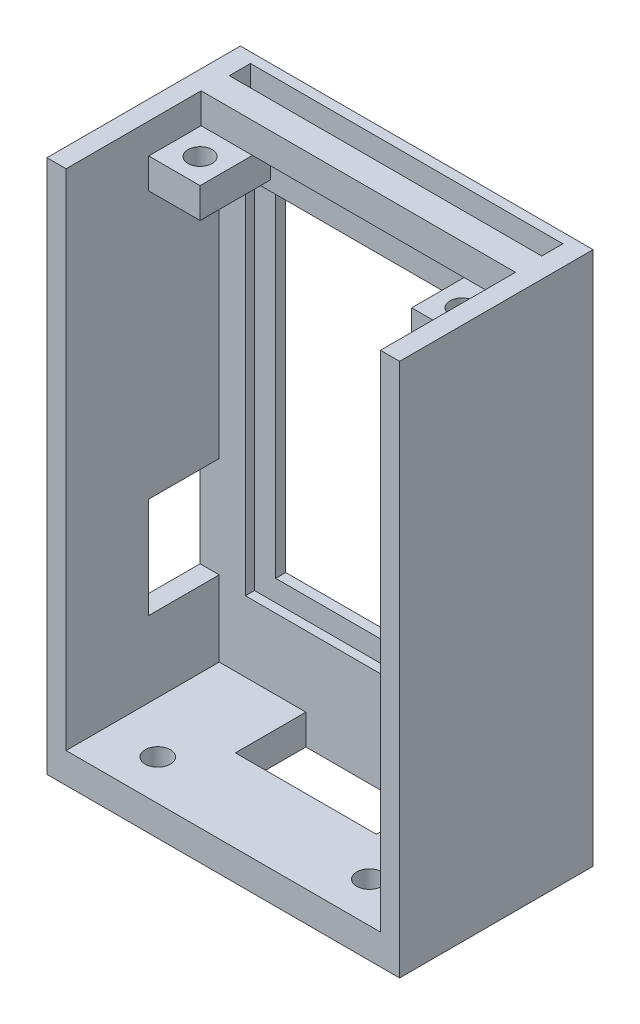
SolidWorks part; units mm, degrees
ref_plane "前视基准面" through (0, 0, 0) normal (0, 0, 1) x (1, 0, 0)
ref_plane "上视基准面" through (0, 0, 0) normal (0, 1, 0) x (1, 0, 0)
ref_plane "右视基准面" through (0, 0, 0) normal (1, 0, 0) x (0, 0, -1)
sketch "草图1" plane through (0, 0, 0) normal (0, 0, 1) x (1, 0, 0)
  line L1 (-15, 20) -> (20, 20)
  line L2 (-15, 20) -> (-15, -33)
  line L3 (-15, -33) -> (20, -33)
  line L4 (20, 20) -> (20, -33)
  dimension "D1" = 53
  dimension "D2" = 35
  dimension "D3" = 15
  dimension "D4" = 20
extrude "凸台-拉伸1" add sketch "草图1" along normal blind 2
sketch "草图2" plane through (0, 0, 2) normal (0, 0, 1) x (1, 0, 0)
  line L0 (-15, 20) -> (-15, -33)
  line L1 (-15, -33) -> (-13, -33)
  line L2 (-15, -33) -> (20, -33) construction
  line L3 (-13, -33) -> (-13, 20)
  line L4 (20, 20) -> (-15, 20) construction
  line L5 (-13, 20) -> (-15, 20)
  line L6 (20, 20) -> (20, -33)
  line L7 (20, -33) -> (18, -33)
  line L8 (18, -33) -> (18, 20)
  line L9 (18, 20) -> (20, 20)
  dimension "D1" = 2
  dimension "D2" = 2
extrude "凸台-拉伸2" add sketch "草图2" along normal blind 13.2
sketch "草图3" plane through (0, 0, 2) normal (0, 0, 1) x (1, 0, 0)
  line L0 (-13, 20) -> (-13, 17)
  line L1 (-13, -33) -> (-13, 20) construction
  line L2 (-13, 17) -> (18, 17)
  line L3 (18, 20) -> (18, -33) construction
  line L4 (18, 17) -> (18, 20)
  line L5 (18, 20) -> (-13, 20)
  line L6 (18, -33) -> (-13, -33)
  line L7 (-13, -33) -> (-13, -30)
  line L8 (-13, -30) -> (18, -30)
  line L9 (18, -30) -> (18, -33)
  dimension "D1" = 3
  dimension "D2" = 3
extrude "凸台-拉伸3" add sketch "草图3" along normal blind 7.2
sketch "草图4" plane through (0, 0, 2) normal (0, 0, 1) x (1, 0, 0)
  line L0 (-13, 17) -> (-13, 14)
  line L1 (-13, -30) -> (-13, 17) construction
  line L2 (-13, 14) -> (18, 14)
  line L3 (18, 17) -> (18, -30) construction
  line L4 (18, 14) -> (18, 17)
  line L5 (18, 17) -> (-13, 17)
  line L6 (-13, -30) -> (18, -30)
  line L7 (18, -30) -> (18, -27)
  line L8 (18, -27) -> (-13, -27)
  line L9 (-13, -27) -> (-13, -30)
  dimension "D1" = 3
  dimension "D2" = 3
extrude "凸台-拉伸4" add sketch "草图4" along normal up to surface (13.2 mm away) up to face at (-14, -6.5, 15.2)
sketch "草图5" plane through (0, 17, 0) normal (0, 1, 0) x (1, 0, 0)
  line L0 (-13, -9.2) -> (18, -9.2) construction
  line L1 (-13, -15.2) -> (-13, -9.2) construction
  line L2 (18, -15.2) -> (18, -9.2) construction
  circle A0 centre (-8, -11.2) radius 1.25
  circle A1 centre (2.5, -11.2) radius 1.25
  circle A2 centre (13, -11.2) radius 1.25
  dimension "D2" = 2.5
  dimension "D3" = 2.5
  dimension "D6" = 2.5
  dimension "D1" = 2
  dimension "D4" = 2
  dimension "D5" = 2
  dimension "D7" = 5
  dimension "D8" = 5
  dimension "D9" = 10.5
extrude "切除-拉伸1" cut sketch "草图5" against normal up to next
sketch "草图7" plane through (0, 0, 15.2) normal (0, 0, 1) x (1, 0, 0)
  line L0 (-13, 17) -> (-13, 14)
  line L1 (-13, 14) -> (18, 14)
  line L2 (18, 14) -> (18, 17)
  line L3 (18, 17) -> (-13, 17)
extrude "切除-拉伸2" cut sketch "草图7" against normal blind 2.2
sketch "草图8" plane through (0, 0, 15.2) normal (0, 0, 1) x (1, 0, 0)
  line L0 (-13, -27) -> (-13, -30)
  line L1 (-13, -30) -> (18, -30)
  line L2 (18, -30) -> (18, -27)
  line L3 (18, -27) -> (-13, -27)
extrude "切除-拉伸3" cut sketch "草图8" against normal blind 2
sketch "草图9" plane through (0, -30, 0) normal (0, -1, 0) x (1, 0, 0)
  line L0 (18, 9.2) -> (-13, 9.2) construction
  line L1 (-13, 13.2) -> (-13, 9.2) construction
  line L2 (18, 13.2) -> (18, 9.2) construction
  circle A0 centre (-8, 11.2) radius 1.25
  circle A1 centre (13, 11.2) radius 1.25
  line M1 (18, 13.2) -> (-13, 13.2)
  line M2 (-13, 13.2) -> (-13, 9.2)
  line M3 (-13, 9.2) -> (18, 9.2)
  line M4 (18, 9.2) -> (18, 13.2)
  dimension "D3" = 2.5
  dimension "D4" = 2.5
  dimension "D1" = 2
  dimension "D2" = 2
  dimension "D5" = 5
  dimension "D6" = 5
sketch "草图10" plane through (0, 0, 13.2) normal (0, 0, 1) x (1, 0, 0)
  line L0 (-3, -27) -> (-3, -30)
  line L1 (18, -27) -> (-13, -27) construction
  line L2 (-13, -30) -> (18, -30) construction
  line L3 (-3, -30) -> (8, -30)
  line L4 (18, -30) -> (-13, -30) construction
  line L5 (8, -30) -> (8, -27)
  line L6 (18, -27) -> (-13, -27) construction
  line L7 (8, -27) -> (-3, -27)
  line L8 (-13, -27) -> (-13, -30) construction
  line L9 (18, -30) -> (18, -27) construction
  dimension "D1" = 10
  dimension "D2" = 10
extrude "切除-拉伸4" cut sketch "草图10" against normal up to surface (4 mm away) up to face at (2.5, -31.5, 9.2)
extrude "切除-拉伸5" cut sketch "草图9" against normal up to surface (3 mm away) contours A0 | A1 region at (-8, -30, 11.2) region at (13, -30, 11.2) up to face at (2.5, -27, 9.4)
sketch "草图12" plane through (0, 0, 15.2) normal (0, 0, 1) x (1, 0, 0)
  line L0 (-15, -22.5) -> (-13, -22.5)
  line L1 (-15, 20) -> (-15, -33) construction
  line L2 (-13, -27) -> (-13, 14) construction
  line L3 (-13, -22.5) -> (-13, -12.5)
  line L4 (-13, -12.5) -> (-15, -12.5)
  line L5 (-15, -12.5) -> (-15, -22.5)
  line L6 (-15, -33) -> (-13, -33) construction
  dimension "D1" = 10.5
  dimension "D2" = 10
sketch "草图13" plane through (0, 0, 2) normal (0, 0, 1) x (1, 0, 0)
  line L0 (-13, -27) -> (-13, 14) construction
  line L1 (-14, 17) -> (19, 17)
  line L2 (-14, 17) -> (-14, -30)
  line L3 (-14, -30) -> (19, -30)
  line L4 (19, 17) -> (19, -30)
  line L5 (-13, 14) -> (18, 14) construction
  dimension "D1" = 33
  dimension "D2" = 47
  dimension "D3" = 1
  dimension "D4" = 3
sketch "草图14" plane through (0, 0, 9.2) normal (0, 0, 1) x (1, 0, 0)
  line L0 (-13, 20) -> (18, 20)
  line L1 (18, 20) -> (18, 17)
  line L2 (18, 17) -> (-13, 17)
  line L3 (-13, 17) -> (-13, 20)
extrude "切除-拉伸8" cut sketch "草图14" against normal blind 5
sketch "草图15" plane through (0, 0, 0) normal (0, 0, -1) x (-1, 0, 0)
  line L0 (15, -33) -> (-20, -33) construction
  line L1 (10.5, -23) -> (-15.5, -23)
  line L2 (10.5, -23) -> (10.5, 13)
  line L3 (10.5, 13) -> (-15.5, 13)
  line L4 (-15.5, -23) -> (-15.5, 13)
  line L5 (15, 20) -> (15, -33) construction
  line M3 (15, -33) -> (15, 20)
  line M4 (15, 20) -> (-20, 20)
  line M5 (-20, 20) -> (-20, -33)
  line M6 (-20, -33) -> (15, -33)
  dimension "D1" = 26
  dimension "D2" = 36
  dimension "D3" = 10
  dimension "D4" = 4.5
extrude "凸台-拉伸5" add sketch "草图15" along normal blind 1 contours L1 L4 L3 L2 M6 M3 M4 M5 region at (2.5, -32.3649, 0)
extrude "切除-拉伸9" cut sketch "草图15<3>" against normal up to surface (2 mm away) up to face at (2.5, -6.5, 2)
sketch "草图15<3>" plane through (0, 0, 0) normal (0, 0, -1) x (-1, 0, 0) same geometry as "草图15"
extrude "凸台-拉伸6" add sketch "草图15<4>" along normal blind 1 contours L1 L4 L3 L2 M6 M3 M4 M5 region at (2.5, -32.3649, 0)
sketch "草图15<4>" plane through (0, 0, 0) normal (0, 0, -1) x (-1, 0, 0) same geometry as "草图15"
extrude "切除-拉伸10" cut sketch "草图14<2>" against normal up to surface (7.2 mm away) up to face at (2.5, -6.5, 2)
sketch "草图14<2>" plane through (0, 0, 9.2) normal (0, 0, 1) x (1, 0, 0) same geometry as "草图14"
sketch "草图21" plane through (0, 0, 13) normal (0, 0, 1) x (1, 0, 0)
  line L0 (-13, 17) -> (-13, 14)
  line L1 (-13, 14) -> (18, 14)
  line L2 (18, 14) -> (18, 17)
  line L3 (18, 17) -> (-13, 17)
extrude "切除-拉伸11" cut sketch "草图21" against normal blind 4
extrude "凸台-拉伸8" add sketch "草图9<6>" along normal up to surface (3 mm away) contours A1 A0 M4 M1 M2 M3 region at (2.5, -30, 11.2) up to face at (2.5, -33, 9.65)
sketch "草图9<6>" plane through (0, -30, 0) normal (0, -1, 0) x (1, 0, 0) same geometry as "草图9"
extrude "切除-拉伸12" cut sketch "草图9<7>" against normal up to surface (3 mm away) contours A1 A0 M4 M1 M2 M3 region at (2.5, -30, 11.2) up to face at (-6.75, -27, 11.2)
sketch "草图9<7>" plane through (0, -30, 0) normal (0, -1, 0) x (1, 0, 0) same geometry as "草图9"
sketch "草图23" plane through (0, 0, 13.2) normal (0, 0, 1) x (1, 0, 0)
  line L0 (-13, -30) -> (-13, -33)
  line L1 (-13, -33) -> (18, -33)
  line L2 (18, -33) -> (18, -30)
  line L3 (18, -30) -> (-13, -30)
extrude "凸台-拉伸9" add sketch "草图23" along normal up to surface (2 mm away) up to face at (-14, -6.5, 15.2)
sketch "草图24" plane through (0, 0, 9.2) normal (0, 0, 1) x (1, 0, 0)
  line L0 (-13, -27) -> (-13, -30)
  line L1 (-13, -30) -> (18, -30)
  line L2 (18, -30) -> (18, -27)
  line L3 (18, -27) -> (-13, -27)
extrude "切除-拉伸13" cut sketch "草图24" against normal up to surface (7.2 mm away) up to face at (2.5, -6.5, 2)
sketch "草图25" plane through (0, 17, 0) normal (0, 1, 0) x (1, 0, 0)
  line L0 (18, -9) -> (18, -2) construction
  line L1 (-14, -2) -> (19, -2) construction
  line L2 (-13, -9) -> (-13, -2) construction
  circle A0 centre (-10.5, -4.5) radius 1.2
  circle A2 centre (15.5, -4.5) radius 1.2
  dimension "D1" = 2.4
  dimension "D2" = 2.5
  dimension "D3" = 2.4
  dimension "D4" = 2.5
  dimension "D5" = 2.5
  dimension "D7" = 2.5
extrude "切除-拉伸14" cut sketch "草图25" against normal up to surface (3 mm away) up to face at (2.5, 14, 5.5)
extrude "凸台-拉伸10" add sketch "草图15<5>" along normal blind 2 contours L1 L4 L3 L2 M6 M3 M4 M5 region at (2.5, -32.3649, 0)
sketch "草图15<5>" plane through (0, 0, 0) normal (0, 0, -1) x (-1, 0, 0) same geometry as "草图15"
sketch "草图28" plane through (0, 20, 0) normal (0, 1, 0) x (1, 0, 0)
  line L0 (-15, -15.2) -> (-15, 2) construction
  line L1 (-13, 1) -> (18, 1)
  line L2 (-13, 1) -> (-13, -1.1)
  line L3 (-13, -1.1) -> (18, -1.1)
  line L4 (18, 1) -> (18, -1.1)
  line L6 (-15, 2) -> (20, 2) construction
  dimension "D1" = 31
  dimension "D2" = 2.1
  dimension "D3" = 2
  dimension "D4" = 1
extrude "切除-拉伸15" cut sketch "草图28" against normal blind 47
extrude "切除-拉伸16" cut sketch "草图21<2>" against normal blind 6
sketch "草图21<2>" plane through (0, 0, 13) normal (0, 0, 1) x (1, 0, 0) same geometry as "草图21"
extrude "切除-拉伸17" cut sketch "草图12" against normal up to surface (13.2 mm away) up to face at (2.5, -8, 2)
extrude "凸台-拉伸11" add sketch "草图12<2>" against normal blind 8.2
sketch "草图12<2>" plane through (0, 0, 15.2) normal (0, 0, 1) x (1, 0, 0) same geometry as "草图12"
sketch "草图32" plane through (0, 0, 7) normal (0, 0, -1) x (-1, 0, 0)
  line L0 (15, -22.5) -> (15, -33.7163) construction
sketch "草图33" plane through (0, -33, 0) normal (0, -1, 0) x (1, 0, 0)
  line L0 (-15, 7) -> (20, 7) construction
  line L1 (20, 15.2) -> (20, -2) construction
  line L2 (9.5, 7) -> (-4.5, 7)
  line L3 (-4.5, 7) -> (-4.5, 2)
  line L4 (-4.5, 2) -> (9.5, 2)
  line L5 (9.5, 2) -> (9.5, 7)
  dimension "D1" = 10.5
  dimension "D2" = 14
  dimension "D3" = 5
extrude "切除-拉伸18" cut sketch "草图33" against normal up to surface (3 mm away) up to face at (2.5, -30, 8.6)
sketch "草图34" plane through (0, 0, 7) normal (0, 0, 1) x (1, 0, 0)
  line L0 (-8, 17) -> (-8, 14)
  line L1 (18, 17) -> (-13, 17) construction
  line L2 (-13, 14) -> (18, 14) construction
  line L3 (-8, 14) -> (13, 14)
  line L4 (-13, 14) -> (18, 14) construction
  line L5 (13, 14) -> (13, 17)
  line L6 (18, 17) -> (-13, 17) construction
  line L7 (13, 17) -> (-8, 17)
  line L8 (-13, 17) -> (-13, 14) construction
  line L9 (18, 14) -> (18, 17) construction
  dimension "D1" = 5
  dimension "D2" = 5
extrude "切除-拉伸19" cut sketch "草图34" against normal up to surface (5 mm away) up to face at (2.5, 18.5, 2)
sketch "草图35" plane through (18, 0, 0) normal (-1, 0, 0) x (0, 0, 1)
  line L1 (-3.4711, 23.5876) -> (25.5027, 23.5876)
  line L2 (-3.4711, 23.5876) -> (-3.4711, -30.5382)
  line L3 (-3.4711, -30.5382) -> (25.5027, -30.5382)
  line L4 (25.5027, 23.5876) -> (25.5027, -30.5382)
  line M5 (2, 17) -> (7, 17)
  line M6 (7, 17) -> (7, 14)
  line M7 (7, 14) -> (2, 14)
  line M8 (2, 14) -> (2, -30)
  line M9 (2, -30) -> (15.2, -30)
  line M10 (15.2, -30) -> (15.2, 20)
  line M11 (15.2, 20) -> (2, 20)
  line M12 (2, 20) -> (2, 17)
extrude "切除-拉伸20" cut sketch "草图35" against normal blind 0.1 contours M12 M5 M6 M7 M8 M9 M10 M11 region at (18, -5.4767, 8.6953)
sketch "草图36" plane through (-13, 0, 0) normal (1, 0, 0) x (0, 0, -1)
  line L1 (-21.5259, 22.8129) -> (9.049, 22.8129)
  line L2 (-21.5259, 22.8129) -> (-21.5259, -34.2568)
  line L3 (-21.5259, -34.2568) -> (9.049, -34.2568)
  line L4 (9.049, 22.8129) -> (9.049, -34.2568)
  line M5 (-2, -30) -> (-2, -22.5)
  line M6 (-2, -22.5) -> (-7, -22.5)
  line M7 (-7, -22.5) -> (-7, -12.5)
  line M8 (-7, -12.5) -> (-2, -12.5)
  line M9 (-2, -12.5) -> (-2, 14)
  line M10 (-2, 14) -> (-7, 14)
  line M11 (-7, 14) -> (-7, 17)
  line M12 (-7, 17) -> (-2, 17)
  line M13 (-2, 17) -> (-2, 20)
  line M14 (-2, 20) -> (-15.2, 20)
  line M15 (-15.2, 20) -> (-15.2, -30)
  line M16 (-15.2, -30) -> (-2, -30)
extrude "切除-拉伸21" cut sketch "草图36" against normal blind 0.1 contours M16 M5 M6 M7 M8 M9 M10 M11 M12 M13 M14 M15 region at (-13, -4.4664, 9.0479)
sketch "草图38" plane through (0, 0, 1.1) normal (0, 0, -1) x (-1, 0, 0)
  line L1 (-22.7972, 22.5547) -> (18.0554, 22.5547)
  line L2 (-22.7972, 22.5547) -> (-22.7972, -33.0172)
  line L3 (-22.7972, -33.0172) -> (18.0554, -33.0172)
  line L4 (18.0554, 22.5547) -> (18.0554, -33.0172)
  line M1 (13, 20) -> (-18, 20)
  line M2 (-18, 20) -> (-18, -27)
  line M3 (-18, -27) -> (13, -27)
  line M4 (13, -27) -> (13, 20)
  line M5 (-15.5, -23) -> (-15.5, 13)
  line M6 (-15.5, 13) -> (10.5, 13)
  line M7 (10.5, 13) -> (10.5, -23)
  line M8 (10.5, -23) -> (-15.5, -23)
extrude "凸台-拉伸12" add sketch "草图38" along normal blind 2 contours M4 M1 M2 M3 M8 M5 M6 M7 region at (-12.437, -3.5, 1.1)
sketch "草图39" plane through (0, 0, 2) normal (0, 0, 1) x (1, 0, 0)
  line L1 (-17.7972, 22.8129) -> (22.1774, 22.8129)
  line L2 (-17.7972, 22.8129) -> (-17.7972, -35.0831)
  line L3 (-17.7972, -35.0831) -> (22.1774, -35.0831)
  line L4 (22.1774, 22.8129) -> (22.1774, -35.0831)
  line M5 (-15, -22.5) -> (-13.1, -22.5)
  line M6 (-13.1, -22.5) -> (-13.1, -30)
  line M7 (-13.1, -30) -> (-4.5, -30)
  line M8 (-4.5, -30) -> (-4.5, -33)
  line M9 (-4.5, -33) -> (9.5, -33)
  line M10 (9.5, -33) -> (9.5, -30)
  line M11 (9.5, -30) -> (18.1, -30)
  line M12 (18.1, -30) -> (18.1, 14)
  line M13 (18.1, 14) -> (13, 14)
  line M14 (13, 14) -> (13, 17)
  line M15 (13, 17) -> (18.1, 17)
  line M16 (18.1, 17) -> (18.1, 20)
  line M17 (18.1, 20) -> (-13.1, 20)
  line M18 (-13.1, 20) -> (-13.1, 17)
  line M19 (-13.1, 17) -> (-8, 17)
  line M20 (-8, 17) -> (-8, 14)
  line M21 (-8, 14) -> (-13.1, 14)
  line M22 (-13.1, 14) -> (-13.1, -12.5)
  line M23 (-13.1, -12.5) -> (-15, -12.5)
  line M24 (-15, -12.5) -> (-15, -22.5)
  line M25 (15.5, -23) -> (-10.5, -23)
  line M26 (-10.5, -23) -> (-10.5, 13)
  line M27 (-10.5, 13) -> (15.5, 13)
  line M28 (15.5, 13) -> (15.5, -23)
extrude "切除-拉伸22" cut sketch "草图39" against normal blind 2 contours M24 M5 M6 M7 M8 M9 M10 M11 M12 M13 M14 M15 M16 M17 M18 M19 M20 M21 M22 M23 M28 M25 M26 M27 region at (-14.3751, -17.5, 2)
sketch "草图40" plane through (0, 0, -2) normal (0, 0, -1) x (-1, 0, 0)
  line L1 (-21.4027, 20.7471) -> (16.5577, 20.7471)
  line L2 (-21.4027, 20.7471) -> (-21.4027, -35.0315)
  line L3 (-21.4027, -35.0315) -> (16.5577, -35.0315)
  line L4 (16.5577, 20.7471) -> (16.5577, -35.0315)
  line M1 (-20, -33) -> (15, -33)
  line M2 (15, -33) -> (15, 20)
  line M3 (15, 20) -> (-20, 20)
  line M4 (-20, 20) -> (-20, -33)
  line M5 (10.5, -23) -> (-15.5, -23)
  line M6 (-15.5, -23) -> (-15.5, 13)
  line M7 (-15.5, 13) -> (10.5, 13)
  line M8 (10.5, 13) -> (10.5, -23)
extrude "凸台-拉伸13" add sketch "草图40" along normal blind 2 contours M4 M1 M2 M3 M8 M5 M6 M7 region at (19.3649, -6.5, -2)
sketch "草图41" plane through (0, 0, -1) normal (0, 0, 1) x (1, 0, 0)
  line L1 (-16.2994, 22.4514) -> (23.5202, 22.4514)
  line L2 (-16.2994, 22.4514) -> (-16.2994, -35.5996)
  line L3 (-16.2994, -35.5996) -> (23.5202, -35.5996)
  line L4 (23.5202, 22.4514) -> (23.5202, -35.5996)
  line M5 (18, 20) -> (-13, 20)
  line M6 (-13, 20) -> (-13, -27)
  line M7 (-13, -27) -> (18, -27)
  line M8 (18, -27) -> (18, 20)
  line M9 (-10.5, -23) -> (-10.5, 13)
  line M10 (-10.5, 13) -> (15.5, 13)
  line M11 (15.5, 13) -> (15.5, -23)
  line M12 (15.5, -23) -> (-10.5, -23)
extrude "切除-拉伸23" cut sketch "草图41" against normal blind 2 contours M8 M5 M6 M7 M12 M9 M10 M11 region at (17.437, -3.5, -1)
sketch "草图42" plane through (0, 0, 0) normal (0, 0, 1) x (1, 0, 0)
  line L0 (-8, 17) -> (13, 17)
  line M16 (13, 17) -> (18.1, 17)
  line M17 (18.1, 17) -> (18.1, 20)
  line M18 (18.1, 20) -> (-13.1, 20)
  line M19 (-13.1, 20) -> (-13.1, 17)
  line M20 (-13.1, 17) -> (-8, 17)
extrude "凸台-拉伸14" add sketch "草图42" along normal blind 1.8 contours L0 M20 M16 M17 M18 M19 region at (2.5, 18.5, 0)
